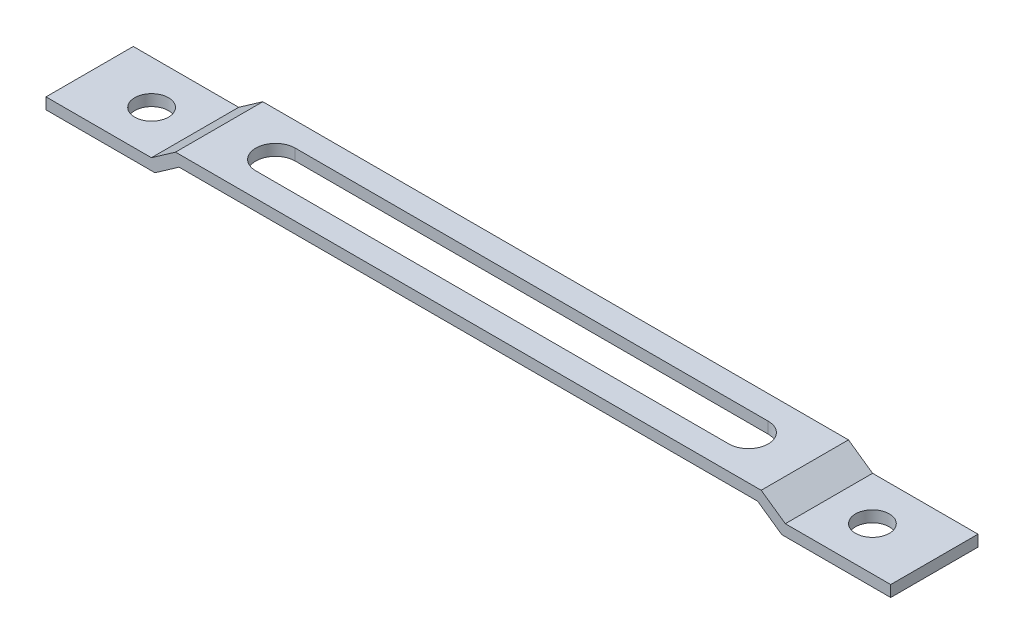
SolidWorks part; units mm, degrees
ref_plane "Спереди" through (0, 0, 0) normal (0, 0, 1) x (1, 0, 0)
ref_plane "Сверху" through (0, 0, 0) normal (0, 1, 0) x (1, 0, 0)
ref_plane "Справа" through (0, 0, 0) normal (1, 0, 0) x (0, 0, -1)
sketch "Эскиз1" plane through (0, 0, 0) normal (0, 0, 1) x (1, 0, 0)
  line L0 (52, 3) -> (-52, 3)
  line L1 (-52, 3) -> (-56.2844, 0)
  line L2 (-56.2844, 0) -> (-75, 0)
  line L3 (0, 38.2597) -> (0, -28.8042) construction
  line L4 (56.2844, 0) -> (75, 0)
  line L5 (52, 3) -> (56.2844, 0)
  point P10 (0, 3)
extrude "Вытянуть-Тонкостенный1" add sketch "Эскиз1" along normal blind 15.5 thin thin type one direction wall 2
sketch "Эскиз2" plane through (0, 3, 0) normal (0, 1, 0) x (1, 0, 0)
  line L0 (0, 11.361) -> (0, -23.4989) construction
  line L1 (-42, -4.25) -> (42, -4.25)
  line L2 (-42, -11.25) -> (42, -11.25)
  arc A0 (-42, -11.25) -> (-42, -4.25) centre (-42, -7.75) cw
  circle A1 centre (-64, -7.75) radius 3
  arc A2 (42, -11.25) -> (42, -4.25) centre (42, -7.75) ccw
  circle A3 centre (64, -7.75) radius 3
  point P11 (0, -4.25)
  point P15 (0, -11.25)
extrude "Вырез-Вытянуть1" cut sketch "Эскиз2" against normal blind 10
